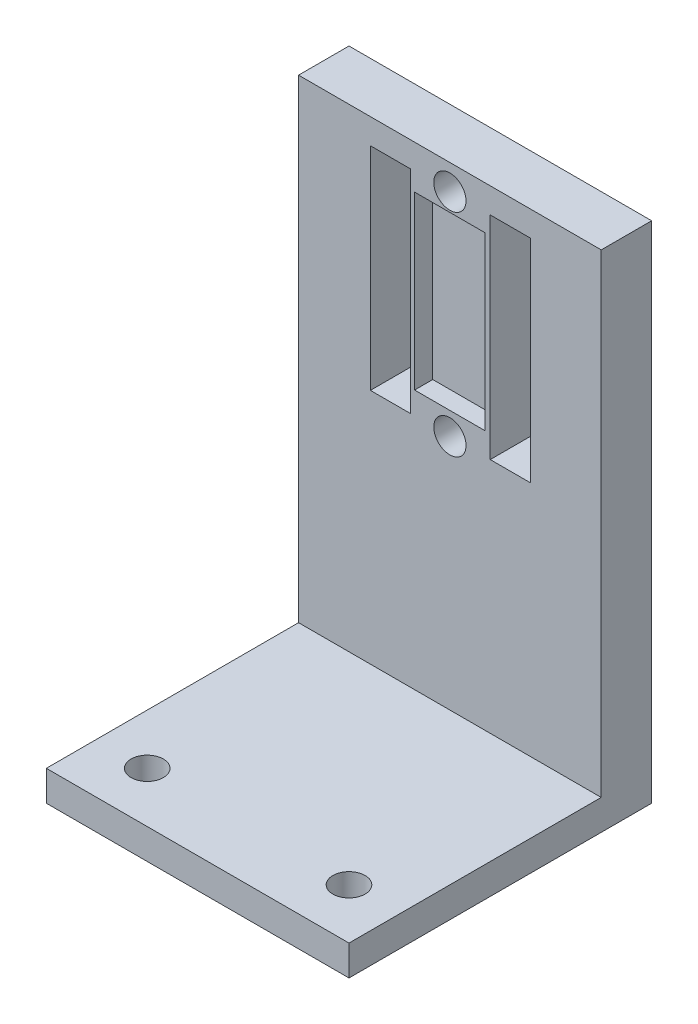
SolidWorks part; units mm, degrees
ref_plane "前视基准面" through (0, 0, 0) normal (0, 0, 1) x (1, 0, 0)
ref_plane "上视基准面" through (0, 0, 0) normal (0, 1, 0) x (1, 0, 0)
ref_plane "右视基准面" through (0, 0, 0) normal (1, 0, 0) x (0, 0, -1)
sketch "草图1" plane through (0, 0, 0) normal (0, 1, 0) x (1, 0, 0)
  line L0 (0, 0) -> (15, 0)
  line L1 (-10, 0) -> (-10, 5) construction
  line L2 (-15, 0) -> (-15, 30)
  line L3 (-15, 30) -> (15, 30)
  line L4 (15, 30) -> (15, 0)
  line L5 (15, 0) -> (15.7841, -0.1253)
  line L6 (0, 0) -> (10, 0)
  line L7 (10, 0) -> (10, 5) construction
  line L8 (0, 0) -> (-10, 0)
  line L9 (-15, 0) -> (-10, 0)
  line L10 (-10, 0) -> (-9.8545, 0.1165)
  line L11 (-10, 5) -> (-10, 25) construction
  line L12 (-15, 25) -> (15, 25)
  line L13 (10, 25) -> (10, 5)
  circle A0 centre (10, 5) radius 1.6
  circle A1 centre (-10, 5) radius 1.6
extrude "凸台-拉伸1" add sketch "草图1" along normal blind 3 contours A0 L12 L2 L9 L8 L0 L4 A1 region at (0, 0, -12.6644)
extrude "凸台-拉伸2" add sketch "草图1<3>" along normal blind 50 contours L2 L12 L4 L3 region at (0, 0, -27.5)
sketch "草图1<3>" plane through (0, 0, 0) normal (0, 1, 0) x (1, 0, 0) same geometry as "草图1"
sketch "草图2" plane through (0, 0, -25) normal (0, 0, 1) x (1, 0, 0)
  line L0 (0, 37) -> (0, 47.5) construction
  line L2 (0, 37) -> (0, 26.5) construction
  line L3 (0, 26.5) -> (4, 26.5) construction
  line L4 (4, 26.5) -> (8, 26.5)
  line L5 (8, 26.5) -> (8, 47.5)
  line L6 (8, 47.5) -> (4, 47.5)
  line L7 (4, 47.5) -> (4, 26.5)
  line L8 (0, 26.5) -> (-3.8799, 26.5) construction
  line L9 (-3.8799, 26.5) -> (-7.8799, 26.5)
  line L10 (-7.8799, 26.5) -> (-7.8799, 47.5)
  line L11 (-7.8799, 47.5) -> (-3.8799, 47.5)
  line L12 (-3.8799, 47.5) -> (-3.8799, 26.5)
  circle A0 centre (0, 47.5) radius 1.6
  circle A1 centre (0, 26.5) radius 1.6
extrude "切除-拉伸1" cut sketch "草图2" against normal through all
sketch "草图3" plane through (0, 0, -25) normal (0, 0, 1) x (1, 0, 0)
  line L0 (-3.5, 45.713) -> (3.5, 45.713)
  line L2 (-3.5, 28.7199) -> (3.5, 28.7199)
  line L3 (3.5, 45.713) -> (3.5, 28.7199)
  line L4 (-3.5, 28.7199) -> (-3.5, 45.713)
extrude "切除-拉伸5" cut sketch "草图3" against normal blind 1.8
